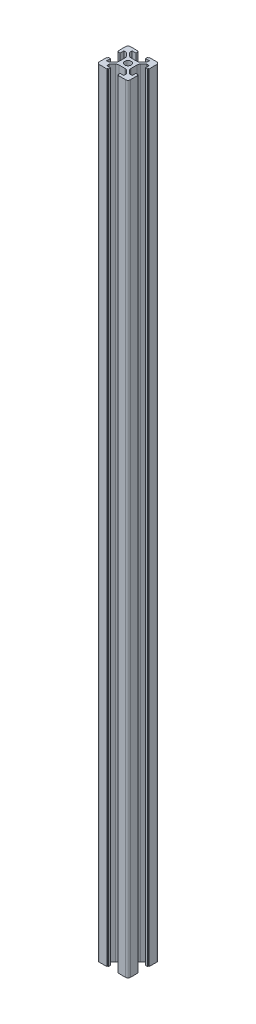
SolidWorks part; units mm, degrees
material "6063-T5"
ref_plane "Front Plane" through (0, 0, 0) normal (0, 0, 1) x (1, 0, 0)
ref_plane "Top Plane" through (0, 0, 0) normal (0, 1, 0) x (1, 0, 0)
ref_plane "Right Plane" through (0, 0, 0) normal (1, 0, 0) x (0, 0, -1)
sketch "Sketch1" plane through (0, 0, 0) normal (0, 1, 0) x (1, 0, 0)
  line L1 (-10, -10) -> (10, -10)
  line L2 (-10, -10) -> (-10, 10)
  line L3 (-10, 10) -> (10, 10)
  line L4 (10, -10) -> (10, 10)
  line L5 (-10, -10) -> (10, 10) construction
  line L6 (-10, 10) -> (10, -10) construction
  circle A0 centre (0, 0) radius 2.1
  point P0 (0, 0)
  dimension "D3" = 4.2
  dimension "D1" = 20
  dimension "D2" = 20
extrude "Boss-Extrude1" add sketch "Sketch1" along normal blind 500
sketch "Sketch2" plane through (0, 500, 0) normal (0, 1, 0) x (1, 0, 0)
  line L14 (-1000, 0) -> (49000, 0) construction
  line L15 (0, -1000) -> (0, 49000) construction
  line L16 (-692.3738, -692.3738) -> (33926.3167, 33926.3167) construction
  line L17 (-2.0109, 3.9) -> (2.0109, 3.9)
  line L18 (-3.4251, 4.4858) -> (-5.5, 6.5607)
  line L23 (10, 10) -> (-10, 10) construction
  line L24 (3.4251, 4.4858) -> (5.5, 6.5607)
  line L29 (3.6, 10) -> (-3.6, 10)
  line L33 (5.5, 8.2) -> (5.5, 6.5607)
  line L34 (5.5, 8.2) -> (3.1, 8.2)
  line L35 (3.1, 8.2) -> (3.1, 9.5)
  line L36 (-5.5, 6.5607) -> (-5.5, 8.2)
  line L37 (-5.5, 8.2) -> (-3.1, 8.2)
  line L38 (-3.1, 8.2) -> (-3.1, 9.5)
  line L39 (-3.6, 10) -> (-3.6, 9.7)
  line L40 (-3.1, 9.5) -> (-3.4, 9.5)
  line L41 (3.1, 9.5) -> (3.4, 9.5)
  line L42 (3.6, 10) -> (3.6, 9.7)
  arc A0 (-3.4251, 4.4858) -> (-2.0109, 3.9) centre (-2.0109, 5.9) ccw
  arc A1 (2.0109, 3.9) -> (3.4251, 4.4858) centre (2.0109, 5.9) ccw
  arc A2 (-3.6, 9.7) -> (-3.4, 9.5) centre (-3.4, 9.7) ccw
  arc A3 (3.4, 9.5) -> (3.6, 9.7) centre (3.4, 9.7) ccw
  dimension "D1" = 2
  dimension "D8" = 0.2
  dimension "D2" = 45
  dimension "D3" = 0.75
  dimension "D4" = 11
  dimension "D5" = 7.2
  dimension "D6" = 6.2
  dimension "D7" = 6.1
  dimension "D9" = 1.8
  dimension "D10" = 0.5
extrude "Cut-Extrude1" cut sketch "Sketch2" against normal through all both and the other way through all
ref_axis "Axis1" through (0, 500, 0) along (0, -1, 0)
pattern_circular "CirPattern1" count 4 over 360 about axis through (0, 500, 0) along (0, -1, 0) of "Cut-Extrude1"
fillet "Fillet1" radius 1.5 4 edges at (10, 250, 10) (10, 250, -10) (-10, 250, 10) (-10, 250, -10)
